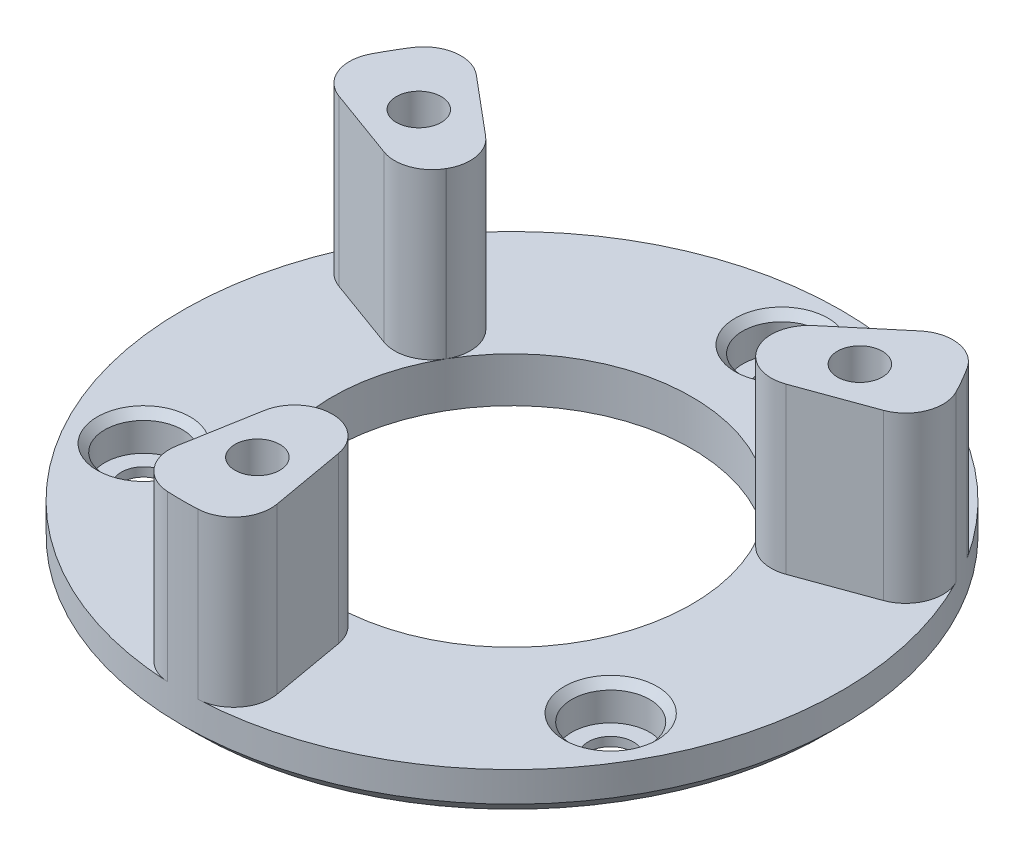
SolidWorks part; units mm, degrees
ref_plane "Front Plane" through (0, 0, 0) normal (0, 0, 1) x (1, 0, 0)
ref_plane "Top Plane" through (0, 0, 0) normal (0, 1, 0) x (1, 0, 0)
ref_plane "Right Plane" through (0, 0, 0) normal (1, 0, 0) x (0, 0, -1)
sketch "Sketch1" plane through (0, 0, 0) normal (0, 1, 0) x (1, 0, 0)
  circle A0 centre (0, 0) radius 12
  circle A1 centre (0, 0) radius 17 construction
  circle A2 centre (0, 0) radius 22
  point P7 (0, 0)
  dimension "D1" = 5
  dimension "D2" = 5
  dimension "D3" = 34
extrude "Boss-Extrude1" add sketch "Sketch1" along normal blind 3
sketch "Sketch3" plane through (0, 3, 0) normal (0, 1, 0) x (1, 0, 0)
  line L0 (-1000, 0) -> (49000, 0) construction
  line L1 (0, 0) -> (14.7224, 8.5) construction
  circle A0 centre (14.7224, 8.5) radius 1.5
  circle A1 centre (0, 18) radius 1.5
  point P8 (0, 0)
  dimension "D3" = 3
  dimension "D5" = 3
  dimension "D1" = 30
  dimension "D2" = 17
  dimension "D4" = 18
extrude "Cut-Extrude2" cut sketch "Sketch3" against normal through all
sketch "Sketch5" plane through (0, 3, 0) normal (0, 1, 0) x (1, 0, 0)
  circle A0 centre (0, 18) radius 2.6
  dimension "D1" = 5.2
extrude "Cut-Extrude3" cut sketch "Sketch5" against normal blind 2.4
pattern_circular "CirPattern1" count 3 over 360 about axis through (0, 0, 0) along (0, 1, 0) of "Cut-Extrude2", "Cut-Extrude3"
sketch "Sketch4" plane through (0, 3, 0) normal (0, 1, 0) x (1, 0, 0)
  line L0 (9.1925, 7.7135) -> (16.853, 14.1413)
  line L1 (11.2763, 4.1042) -> (20.6732, 7.5244)
  line L2 (0, 0) -> (28.602, 10.4103) construction
  line L3 (0, 0) -> (22.9613, 19.2668) construction
  line L4 (-1000, 0) -> (49000, 0) construction
  circle A0 centre (0, 0) radius 22 construction
  circle A1 centre (0, 0) radius 12 construction
  arc A2 (20.6732, 7.5244) -> (16.853, 14.1413) centre (0, 0) ccw
  arc A3 (11.2763, 4.1042) -> (9.1925, 7.7135) centre (0, 0) ccw
  circle A4 centre (14.7224, 8.5) radius 1.5
  dimension "D1" = 20
  dimension "D2" = 40
extrude "Boss-Extrude2" add sketch "Sketch4" along normal blind 11
pattern_circular "CirPattern2" count 3 over 360 about axis through (0, 0, 0) along (0, 1, 0) of "Boss-Extrude2"
fillet "Fillet1" radius 2.5 12 edges at (9.1925, 8.5, -7.7135) (11.2763, 8.5, -4.1042) (20.6732, 8.5, -7.5244) (16.853, 8.5, -14.1413) (-11.2763, 8.5, -4.1042) (-9.1925, 8.5, -7.7135) (-16.853, 8.5, -14.1413) (-20.6732, 8.5, -7.5244) (2.0838, 8.5, 11.8177) (-2.0838, 8.5, 11.8177) (-3.8203, 8.5, 21.6658) (3.8203, 8.5, 21.6658)
chamfer "Chamfer1" distance 0.5 angle 45 3 edges at (-13.3368, 3, 7.7) (0, 3, -15.4) (13.3368, 3, 7.7)
chamfer "Chamfer2" distance 1 angle 45 1 edges at (0, 0, 22)
